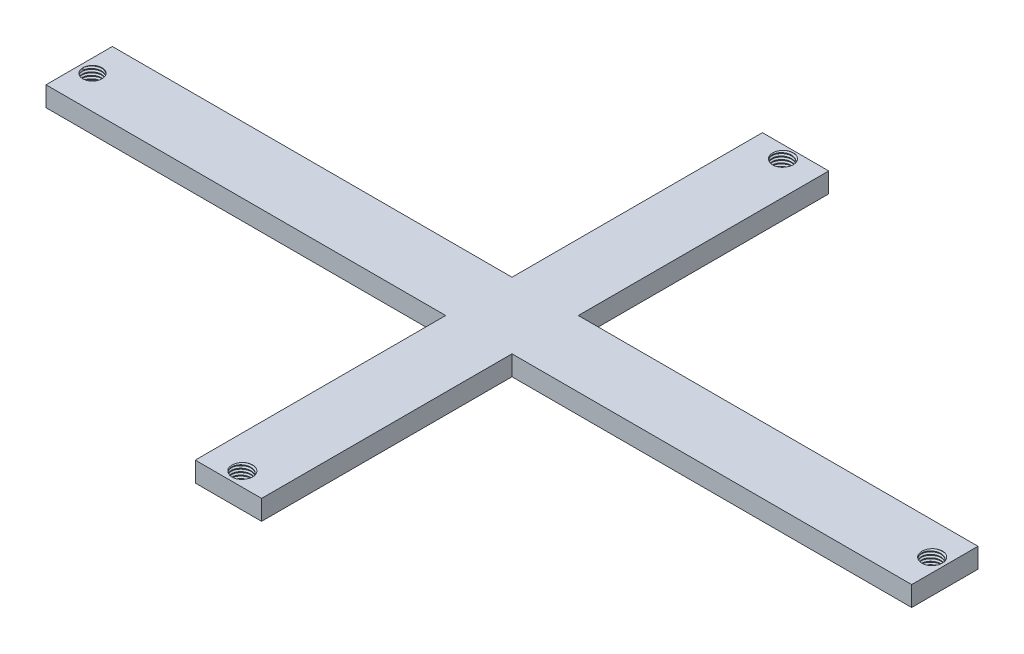
SolidWorks part; units mm, degrees
ref_plane "Front Plane" through (0, 0, 0) normal (0, 0, 1) x (1, 0, 0)
ref_plane "Top Plane" through (0, 0, 0) normal (0, 1, 0) x (1, 0, 0)
ref_plane "Right Plane" through (0, 0, 0) normal (1, 0, 0) x (0, 0, -1)
sketch "Sketch1" plane through (0, 0, 0) normal (0, 1, 0) x (1, 0, 0)
  line L1 (-25.0426, 7.6471) -> (105.4574, 7.6471)
  line L2 (-25.0426, 7.6471) -> (-25.0426, -2.3529)
  line L3 (-25.0426, -2.3529) -> (105.4574, -2.3529)
  line L4 (105.4574, 7.6471) -> (105.4574, -2.3529)
  line L5 (35.2074, 45.3971) -> (45.2074, 45.3971)
  line L6 (35.2074, 45.3971) -> (35.2074, -40.1029)
  line L7 (35.2074, -40.1029) -> (45.2074, -40.1029)
  line L8 (45.2074, 45.3971) -> (45.2074, -40.1029)
  dimension "D1" = 10
  dimension "D2" = 10
  dimension "D3" = 130.5
  dimension "D4" = 85.5
  dimension "D5" = 60.25
  dimension "D6" = 37.75
extrude "Boss-Extrude1" add sketch "Sketch1" along normal blind 3 contours L8 L1 L6 L3 | L6 L1 L2 L3 | L8 L5 L6 L1 | L8 L3 L6 L7 | L3 L4 L1 L2 region at (5.0824, 0, -2.6471) region at (40.2074, 0, -26.5221) region at (40.2074, 0, -2.6471) region at (40.2074, 0, 21.2279)
sketch "Sketch2" plane through (0, 3, 0) normal (0, 1, 0) x (1, 0, 0)
  line L0 (-25.0426, 7.6471) -> (35.2074, 7.6471) construction
  line L1 (-25.0426, 7.6471) -> (-25.0426, -2.3529) construction
  circle A0 centre (-23.0426, 2.6471) radius 1.25
  point P4 (0, 0)
  dimension "D1" = 2.5
  dimension "D2" = 5
  dimension "D3" = 2
sketch "Sketch6" plane through (0, 3, 0) normal (0, 1, 0) x (1, 0, 0)
  line L0 (35.2074, 45.3971) -> (45.2074, 45.3971) construction
  line L1 (45.2074, 45.3971) -> (45.2074, 7.6471) construction
  line L2 (105.4574, 7.6471) -> (105.4574, -2.3529) construction
  line L3 (45.2074, -2.3529) -> (105.4574, -2.3529) construction
  line L4 (35.2074, -40.1029) -> (45.2074, -40.1029) construction
  line L5 (35.2074, -2.3529) -> (35.2074, -40.1029) construction
  circle A0 centre (40.2074, 43.3971) radius 1.25
  circle A1 centre (103.4574, 2.6471) radius 1.25
  circle A2 centre (40.2074, -38.1029) radius 1.25
  dimension "D1" = 2.5
  dimension "D2" = 2.5
  dimension "D3" = 2.5
  dimension "D4" = 2
  dimension "D5" = 5
  dimension "D6" = 2
  dimension "D7" = 5
  dimension "D8" = 2
  dimension "D9" = 5
hole_wizard "M2.5 Clearance Hole1" positions "Sketch22" profile "Sketch23" hole size "M2.5" standard "ANSI Metric"
sketch "Sketch22" plane through (0, 3, 0) normal (0, 1, 0) x (1, 0, 0)
  point P0 (-23.0426, 2.6471)
sketch "Sketch23" plane through (-23.0426, 3, -2.6471) normal (1, 0, 0) x (0, 0, 1)
  line L0 (0, 0) -> (0, 3.8712)
  line L1 (0, 3.8712) -> (1.45, 3)
  line L2 (1.45, 3) -> (1.45, 0)
  line L5 (1.45, 0) -> (0, 0)
  line L10 (0, 3.8712) -> (-1.45, 3) construction
  line L11 (0, -6.35) -> (0, 107.95) construction
  dimension "Hole Dia." = 2.9
  dimension "Hole Depth" = 3
  dimension "Drill Angle" = 118
hole_wizard "M2.5 Clearance Hole2" positions "Sketch24" profile "Sketch25" hole size "M2.5" standard "ANSI Metric"
sketch "Sketch24" plane through (0, 3, 0) normal (0, 1, 0) x (1, 0, 0)
  point P0 (40.2074, 43.3971)
sketch "Sketch25" plane through (40.2074, 3, -43.3971) normal (1, 0, 0) x (0, 0, 1)
  line L0 (0, 0) -> (0, 3.8712)
  line L1 (0, 3.8712) -> (1.45, 3)
  line L2 (1.45, 3) -> (1.45, 0)
  line L5 (1.45, 0) -> (0, 0)
  line L10 (0, 3.8712) -> (-1.45, 3) construction
  line L11 (0, -6.35) -> (0, 107.95) construction
  dimension "Hole Dia." = 2.9
  dimension "Hole Depth" = 3
  dimension "Drill Angle" = 118
hole_wizard "M2.5 Clearance Hole3" positions "Sketch26" profile "Sketch27" hole size "M2.5" standard "ANSI Metric"
sketch "Sketch26" plane through (0, 3, 0) normal (0, 1, 0) x (1, 0, 0)
  point P0 (103.4574, 2.6471)
sketch "Sketch27" plane through (103.4574, 3, -2.6471) normal (1, 0, 0) x (0, 0, 1)
  line L0 (0, 0) -> (0, 3.8712)
  line L1 (0, 3.8712) -> (1.45, 3)
  line L2 (1.45, 3) -> (1.45, 0)
  line L5 (1.45, 0) -> (0, 0)
  line L10 (0, 3.8712) -> (-1.45, 3) construction
  line L11 (0, -6.35) -> (0, 107.95) construction
  dimension "Hole Dia." = 2.9
  dimension "Hole Depth" = 3
  dimension "Drill Angle" = 118
hole_wizard "M2.5 Clearance Hole4" positions "Sketch28" profile "Sketch29" hole size "M2.5" standard "ANSI Metric"
sketch "Sketch28" plane through (0, 3, 0) normal (0, 1, 0) x (1, 0, 0)
  point P0 (40.2074, -38.1029)
sketch "Sketch29" plane through (40.2074, 3, 38.1029) normal (1, 0, 0) x (0, 0, 1)
  line L0 (0, 0) -> (0, 3.8712)
  line L1 (0, 3.8712) -> (1.45, 3)
  line L2 (1.45, 3) -> (1.45, 0)
  line L5 (1.45, 0) -> (0, 0)
  line L10 (0, 3.8712) -> (-1.45, 3) construction
  line L11 (0, -6.35) -> (0, 107.95) construction
  dimension "Hole Dia." = 2.9
  dimension "Hole Depth" = 3
  dimension "Drill Angle" = 118
thread "Thread4" pitch 0.45 method cut profile "Thread Profile4" start angle 0, offset 0, length 0, pitch 0.45, diameter 2.9
ref_plane "Plane4" through (-24.4926, 3, -2.6471) normal (0, 0, 1) x (-1, 0, 0)
sketch "Thread Profile4" plane through (-24.4926, 3, -2.6471) normal (0, 0, 1) x (-1, 0, 0)
  line L0 (0, 0) -> (0, 0.45) construction
  line L1 (0, 0) -> (0.2436, 0.1406)
  line L2 (0.2436, 0.1406) -> (0.2436, 0.1969)
  line L3 (0.2436, 0.1969) -> (0, 0.3375)
  line L4 (0.2436, 0.1687) -> (0, 0.1687) construction
  line L11 (0, 0) -> (0, 0.3375)
  point P2 (0, 0)
  dimension "Pitch" = 0.45
  dimension "Profile_Angle" = 60
  dimension "Profile_Land" = 0.0562
  dimension "Profile_Height" = 0.2436
thread "Thread5" pitch 0.45 method cut profile "Thread Profile5" start angle 0, offset 0, length 0, pitch 0.45, diameter 2.9
ref_plane "Plane5" through (41.6574, 0, -43.3971) normal (0, 0, 1) x (1, 0, 0)
sketch "Thread Profile5" plane through (41.6574, 0, -43.3971) normal (0, 0, 1) x (1, 0, 0)
  line L0 (0, 0) -> (0, 0.45) construction
  line L1 (0, 0) -> (0.2436, 0.1406)
  line L2 (0.2436, 0.1406) -> (0.2436, 0.1969)
  line L3 (0.2436, 0.1969) -> (0, 0.3375)
  line L4 (0.2436, 0.1687) -> (0, 0.1687) construction
  line L11 (0, 0) -> (0, 0.3375)
  point P2 (0, 0)
  dimension "Pitch" = 0.45
  dimension "Profile_Angle" = 60
  dimension "Profile_Land" = 0.0562
  dimension "Profile_Height" = 0.2436
thread "Thread6" pitch 0.45 method cut profile "Thread Profile6" start angle 0, offset 0, length 0, pitch 0.45, diameter 2.9
ref_plane "Plane6" through (104.9074, 0, -2.6471) normal (0, 0, 1) x (1, 0, 0)
sketch "Thread Profile6" plane through (104.9074, 0, -2.6471) normal (0, 0, 1) x (1, 0, 0)
  line L0 (0, 0) -> (0, 0.45) construction
  line L1 (0, 0) -> (0.2436, 0.1406)
  line L2 (0.2436, 0.1406) -> (0.2436, 0.1969)
  line L3 (0.2436, 0.1969) -> (0, 0.3375)
  line L4 (0.2436, 0.1687) -> (0, 0.1687) construction
  line L11 (0, 0) -> (0, 0.3375)
  point P2 (0, 0)
  dimension "Pitch" = 0.45
  dimension "Profile_Angle" = 60
  dimension "Profile_Land" = 0.0562
  dimension "Profile_Height" = 0.2436
thread "Thread7" pitch 0.45 method cut profile "Thread Profile7" start angle 0, offset 0, length 0, pitch 0.45, diameter 2.9
ref_plane "Plane7" through (41.6574, 0, 38.1029) normal (0, 0, 1) x (1, 0, 0)
sketch "Thread Profile7" plane through (41.6574, 0, 38.1029) normal (0, 0, 1) x (1, 0, 0)
  line L0 (0, 0) -> (0, 0.45) construction
  line L1 (0, 0) -> (0.2436, 0.1406)
  line L2 (0.2436, 0.1406) -> (0.2436, 0.1969)
  line L3 (0.2436, 0.1969) -> (0, 0.3375)
  line L4 (0.2436, 0.1687) -> (0, 0.1687) construction
  line L11 (0, 0) -> (0, 0.3375)
  point P2 (0, 0)
  dimension "Pitch" = 0.45
  dimension "Profile_Angle" = 60
  dimension "Profile_Land" = 0.0562
  dimension "Profile_Height" = 0.2436
